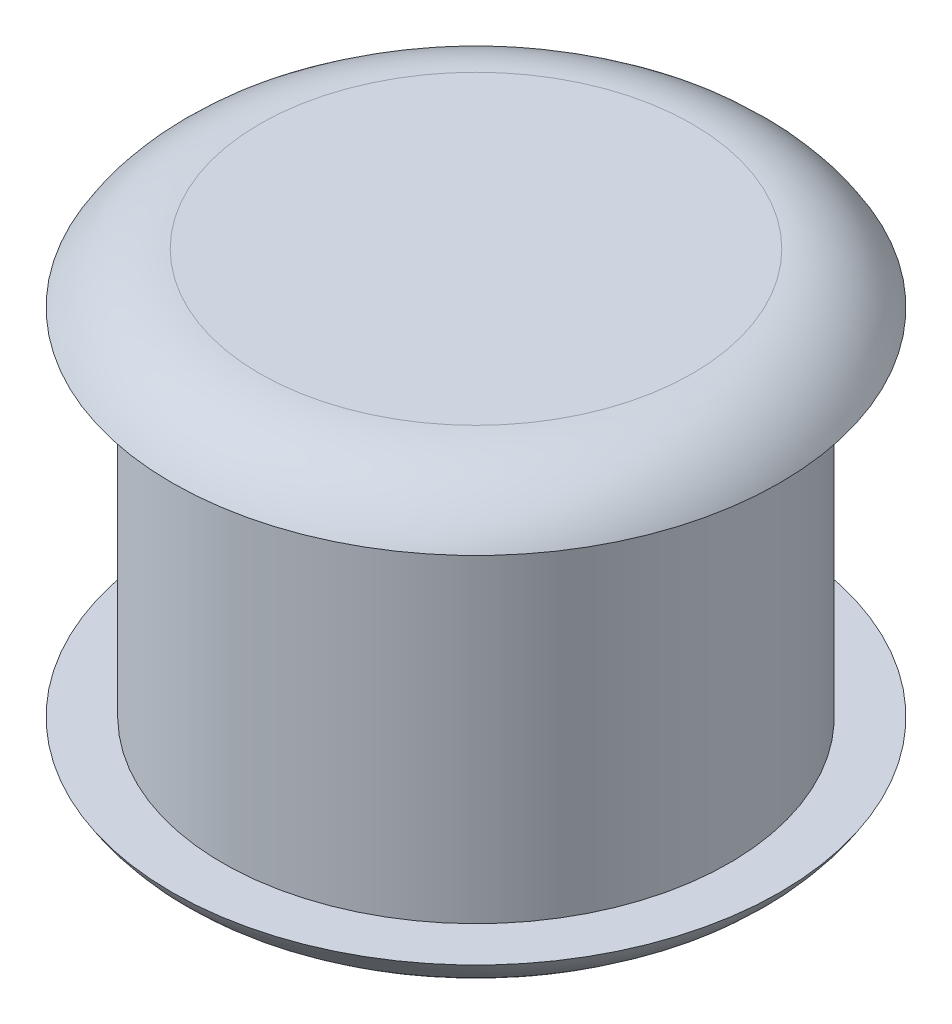
SolidWorks part; units mm, degrees
material "Alloy Steel"
ref_plane "Front Plane" through (0, 0, 0) normal (0, 0, 1) x (1, 0, 0)
ref_plane "Top Plane" through (0, 0, 0) normal (0, 1, 0) x (1, 0, 0)
ref_plane "Right Plane" through (0, 0, 0) normal (1, 0, 0) x (0, 0, -1)
sketch "Sketch2" plane through (0, 0, 0) normal (0, 0, 1) x (1, 0, 0)
  line L0 (0, 0) -> (304.8, 0)
  line L1 (304.8, 0) -> (304.8, -50.8)
  line L2 (304.8, -50.8) -> (254, -50.8)
  line L3 (254, -50.8) -> (254, -406.4)
  line L4 (254, -406.4) -> (304.8, -406.4)
  line L5 (304.8, -406.4) -> (304.8, -457.2)
  line L6 (304.8, -457.2) -> (0, -457.2)
  line L7 (0, -457.2) -> (0, 0)
  dimension "D1" = 457.2
  dimension "D2" = 355.6
  dimension "D3" = 50.8
  dimension "D4" = 254
  dimension "D5" = 50.8
  dimension "D6" = 50.8
revolve "Revolve1" add sketch "Sketch2" angle 360 about L7
fillet "Fillet1" radius 101.6 2 edges at (0, -457.2, -304.8) (0, 0, -304.8)
scale "Scale1" scale about centroid uniform scaling yes scale factor 0.214286
